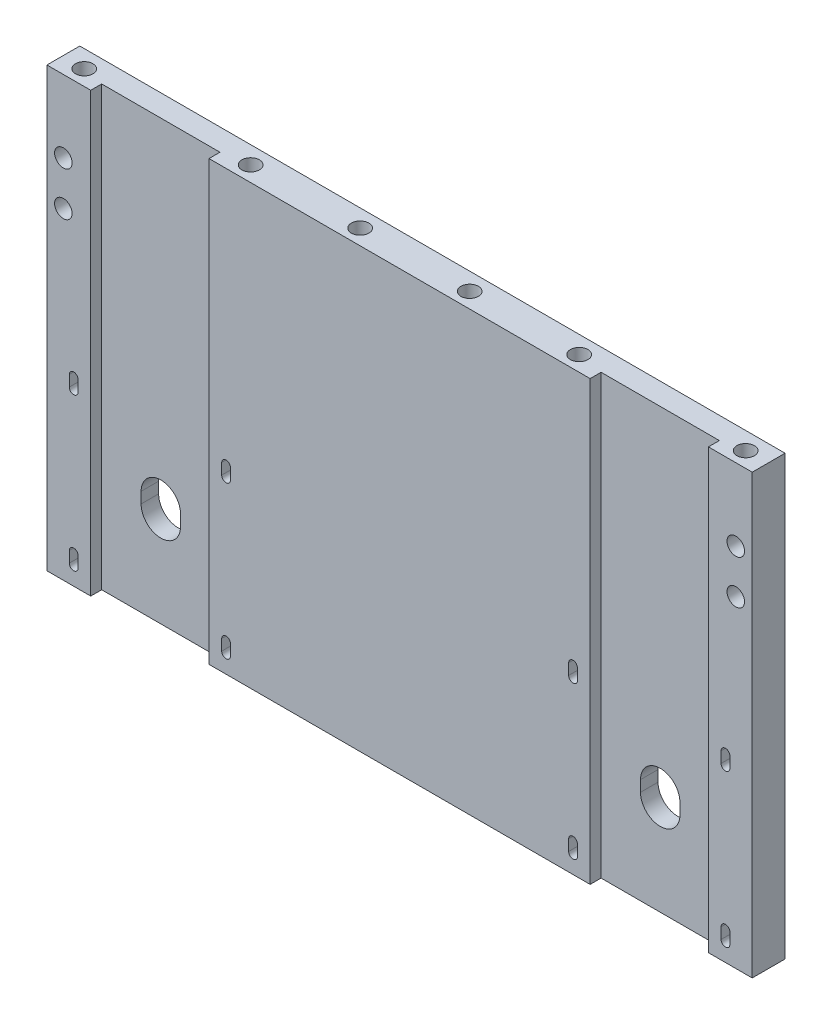
SolidWorks part; units mm, degrees
ref_plane "Płaszczyzna przednia" through (0, 0, 0) normal (0, 0, 1) x (1, 0, 0)
ref_plane "Płaszczyzna górna" through (0, 0, 0) normal (0, 1, 0) x (1, 0, 0)
ref_plane "Płaszczyzna prawa" through (0, 0, 0) normal (1, 0, 0) x (0, 0, -1)
sketch "Szkic1" plane through (0, 0, 0) normal (0, 0, 1) x (1, 0, 0)
  line L1 (161, -100) -> (-161, -100)
  line L2 (161, -100) -> (161, 100)
  line L3 (161, 100) -> (-161, 100)
  line L4 (-161, -100) -> (-161, 100)
  line L5 (161, -100) -> (-161, 100) construction
  line L6 (161, 100) -> (-161, -100) construction
  point P0 (0, 0)
  dimension "D1" = 322
  dimension "D2" = 200
extrude "Dodanie-wyciągnięcie1" add sketch "Szkic1" along normal blind 15
sketch "Szkic3" plane through (0, 0, 15) normal (0, 0, 1) x (1, 0, 0)
  line L0 (161, 100) -> (-161, 100) construction
  line L1 (-141, 100) -> (-87, 100)
  line L2 (-141, 100) -> (-141, -100)
  line L3 (-141, -100) -> (-87, -100)
  line L4 (-87, 100) -> (-87, -100)
  line L5 (-161, -100) -> (161, -100) construction
  line L6 (-161, 100) -> (-161, -100) construction
  line L7 (161, -100) -> (161, 100) construction
  line L8 (87, 100) -> (141, 100)
  line L9 (87, 100) -> (87, -100)
  line L10 (87, -100) -> (141, -100)
  line L11 (141, 100) -> (141, -100)
  dimension "D1" = 54
  dimension "D2" = 20
  dimension "D3" = 54
  dimension "D4" = 20
extrude "Wytnij-wyciągnięcie1" cut sketch "Szkic3" against normal blind 5
sketch "Szkic2" plane through (0, 0, 15) normal (0, 0, 1) x (1, 0, 0)
  line L0 (-161, -100) -> (-141, -100) construction
  line L1 (-161, 100) -> (-161, -100) construction
  line L3 (-150.8, -86.87) -> (-146.8, -86.87)
  line L4 (-150.8, -86.87) -> (-150.8, -91.87)
  line L5 (-150.8, -91.87) -> (-146.8, -91.87)
  line L6 (-146.8, -86.87) -> (-146.8, -91.87)
  circle A0 centre (-148.8, -91.87) radius 2
  circle A1 centre (-148.8, -86.87) radius 2
  dimension "D1" = 8.13
  dimension "D2" = 12.2
  dimension "D3" = 5
  dimension "D4" = 4
  dimension "D5" = 4
extrude "Wytnij-wyciągnięcie2" cut sketch "Szkic2" against normal blind 17.75 contours L3 A1 | L3 A1 | A1 L4 A0 L6 | L5 A0 | L5 A0 region at (-148.8, -86.0212, 15) region at (-148.8, -89.37, 15) region at (-148.8, -87.7188, 15) region at (-148.8, -91.0212, 15) region at (-148.8, -92.7188, 15)
pattern_linear "Szyk liniowy1" count 2 spacing 69.6 along (1, 0, 0) count 2 spacing 69.6 along (0, 1, 0) of "Wytnij-wyciągnięcie2"
sketch "Szkic5" plane through (0, 0, 0) normal (0, 0, -1) x (-1, 0, 0)
  line L0 (161, -100) -> (-161, -100) construction
  line L4 (161, 100) -> (161, -100) construction
  line L10 (150.5, -57.07) -> (77.5, -57.07)
  line L11 (150.5, -57.07) -> (150.5, -52.07)
  line L12 (150.5, -52.07) -> (77.5, -52.07)
  line L13 (77.5, -57.07) -> (77.5, -52.07)
  circle A0 centre (114, -57.07) radius 36.5
  circle A1 centre (114, -52.07) radius 36.5
  dimension "D1" = 42.93
  dimension "D3" = 73
  dimension "D4" = 5
  dimension "D5" = 73
  dimension "D2" = 47
extrude "Wytnij-wyciągnięcie3" cut sketch "Szkic5" against normal blind 2 contours L12 A1 A0 | L12 A0 | A0 A1 L10 L12 | L10 A1 | A1 L10 A0 | L12 A1 A0 | A1 A0 L10 | A1 L13 A0 | A0 A1 L12 | A1 L10 A0 | A1 A0 L11 | A1 region at (-114, -92.7538, 0) region at (-150.4743, -54.57, 0) region at (-150.3711, -56.2371, 0) region at (-114, -70.296, 0) region at (-114, -54.57, 0) region at (-150.3711, -52.9029, 0) region at (-150.328, -51.2538, 0) region at (-77.6289, -56.2371, 0) region at (-77.5257, -54.57, 0) region at (-114, -38.844, 0) region at (-77.6289, -52.9029, 0)
sketch "Szkic7" plane through (0, 0, 2) normal (0, 0, -1) x (-1, 0, 0)
  line L1 (105, -52.07) -> (123, -52.07)
  line L2 (105, -52.07) -> (105, -57.07)
  line L3 (105, -57.07) -> (123, -57.07)
  line L4 (123, -52.07) -> (123, -57.07)
  circle A0 centre (114, -57.07) radius 9
  arc A2 (77.5, -57.07) -> (150.5, -57.07) centre (114, -57.07) ccw construction
  circle A3 centre (114, -52.07) radius 9
  point P8 (114, -93.57)
  dimension "D1" = 18
  dimension "D2" = 18
extrude "Wytnij-wyciągnięcie4" cut sketch "Szkic7" against normal blind 17.75 contours A3 L3 A0 | L3 A3 | A0 A3 L3 L1 | A3 A0 L3 | L1 A3 A0 | L1 A3 A0 | A3 L2 A0 | L1 A0 | A0 A3 L1 | A3 A0 L4 | A3 L3 A0 region at (-114, -47.1697, 2) region at (-105.1059, -54.57, 2) region at (-105.5557, -52.8954, 2) region at (-114, -50.435, 2) region at (-114, -54.57, 2) region at (-105.5557, -56.2446, 2) region at (-114, -61.9703, 2) region at (-122.4443, -52.8954, 2) region at (-122.8941, -54.57, 2) region at (-114, -58.705, 2) region at (-122.4443, -56.2446, 2)
pattern_linear "Szyk liniowy2" count 2 spacing 228 along (1, 0, 0) of "Wytnij-wyciągnięcie2", "Szyk liniowy1", "Wytnij-wyciągnięcie3", "Wytnij-wyciągnięcie4"
sketch "Szkic8" plane through (0, 100, 0) normal (0, 1, 0) x (1, 0, 0)
  line L0 (-161, -15) -> (-161, 0) construction
  line L1 (-141, -15) -> (-161, -15) construction
  line L2 (161, -15) -> (161, 0) construction
  line L3 (161, -15) -> (141, -15) construction
  circle A0 centre (-151, -8) radius 4
  circle A1 centre (151, -8) radius 4
  dimension "D1" = 10
  dimension "D3" = 8
  dimension "D6" = 8
  dimension "D2" = 7
  dimension "D4" = 10
  dimension "D5" = 7
extrude "Wytnij-wyciągnięcie5" cut sketch "Szkic8" against normal blind 20
sketch "Szkic9" plane through (0, 100, 0) normal (0, 1, 0) x (1, 0, 0)
  line L0 (87, -15) -> (-87, -15) construction
  line L1 (-87, -10) -> (-87, -15) construction
  circle A0 centre (-75, -8) radius 4
  dimension "D1" = 8
  dimension "D2" = 7
  dimension "D3" = 12
extrude "Wytnij-wyciągnięcie6" cut sketch "Szkic9" against normal blind 20
pattern_linear "Szyk liniowy3" count 4 spacing 50 along (1, 0, 0) of "Wytnij-wyciągnięcie6"
sketch "Szkic10" plane through (0, 0, 15) normal (0, 0, 1) x (1, 0, 0)
  line L0 (-141, 100) -> (-161, 100) construction
  line L1 (-161, 100) -> (-161, -100) construction
  circle A0 centre (-153.5, 67) radius 4
  circle A1 centre (-153.5, 47) radius 4
  dimension "D1" = 53
  dimension "D3" = 8
  dimension "D4" = 8
  dimension "D2" = 20
  dimension "D5" = 7.5
extrude "Wytnij-wyciągnięcie7" cut sketch "Szkic10" against normal blind 20
sketch "Szkic11" plane through (0, 0, 15) normal (0, 0, 1) x (1, 0, 0)
  line L0 (161, 100) -> (141, 100) construction
  line L1 (161, -100) -> (161, 100) construction
  circle A0 centre (153.5, 47) radius 4
  circle A1 centre (153.5, 67) radius 4
  dimension "D1" = 53
  dimension "D2" = 8
  dimension "D3" = 8
  dimension "D4" = 7.5
  dimension "D5" = 20
extrude "Wytnij-wyciągnięcie8" cut sketch "Szkic11" against normal blind 20
